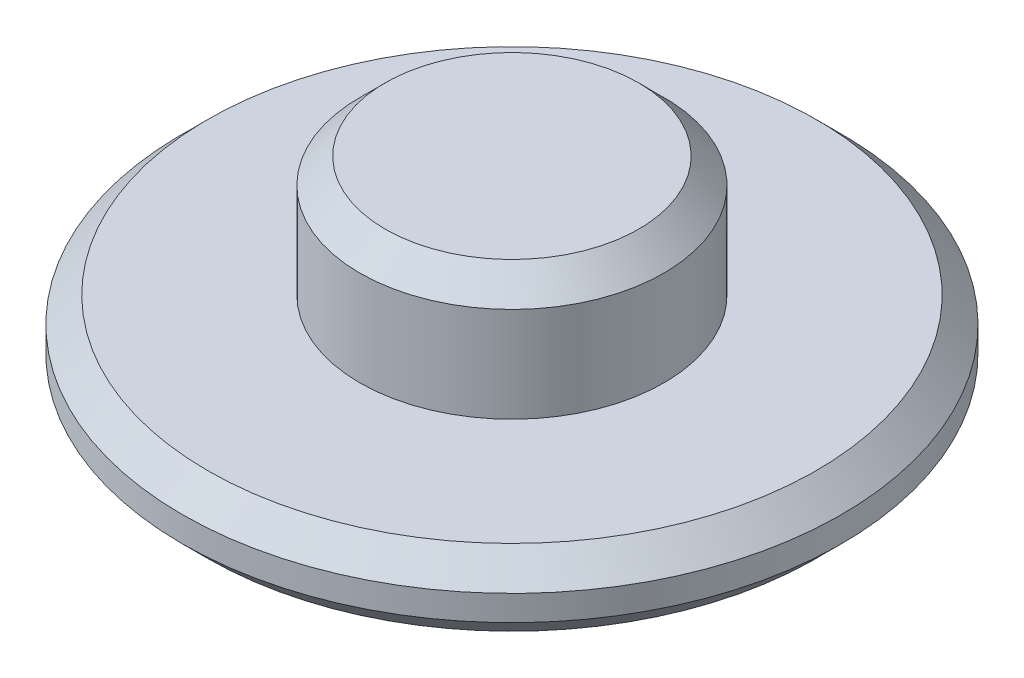
SolidWorks part; units mm, degrees
ref_plane "Alzado" through (0, 0, 0) normal (0, 0, 1) x (1, 0, 0)
ref_plane "Planta" through (0, 0, 0) normal (0, 1, 0) x (1, 0, 0)
ref_plane "Vista lateral" through (0, 0, 0) normal (1, 0, 0) x (0, 0, -1)
sketch "Croquis1" plane through (0, 0, 0) normal (0, 1, 0) x (1, 0, 0)
  circle A0 centre (0, 0) radius 6
  circle A1 centre (0, 0) radius 13
  dimension "D1" = 12
  dimension "D2" = 26
extrude "Saliente-Extruir1" add sketch "Croquis1" along normal blind 4.75 contours A0 region at (0, 0, 0)
extrude "Saliente-Extruir2" add sketch "Croquis1<3>" against normal blind 3 contours A1 A0 | A0 region at (0, 0, 0) region at (-12.6323, 0, 0)
sketch "Croquis1<3>" plane through (0, 0, 0) normal (0, 1, 0) x (1, 0, 0) same geometry as "Croquis1"
chamfer "Chaflán1" distance 1 angle 45 3 edges at (0, 4.75, 6) (0, -3, 13) (0, 0, 13)
